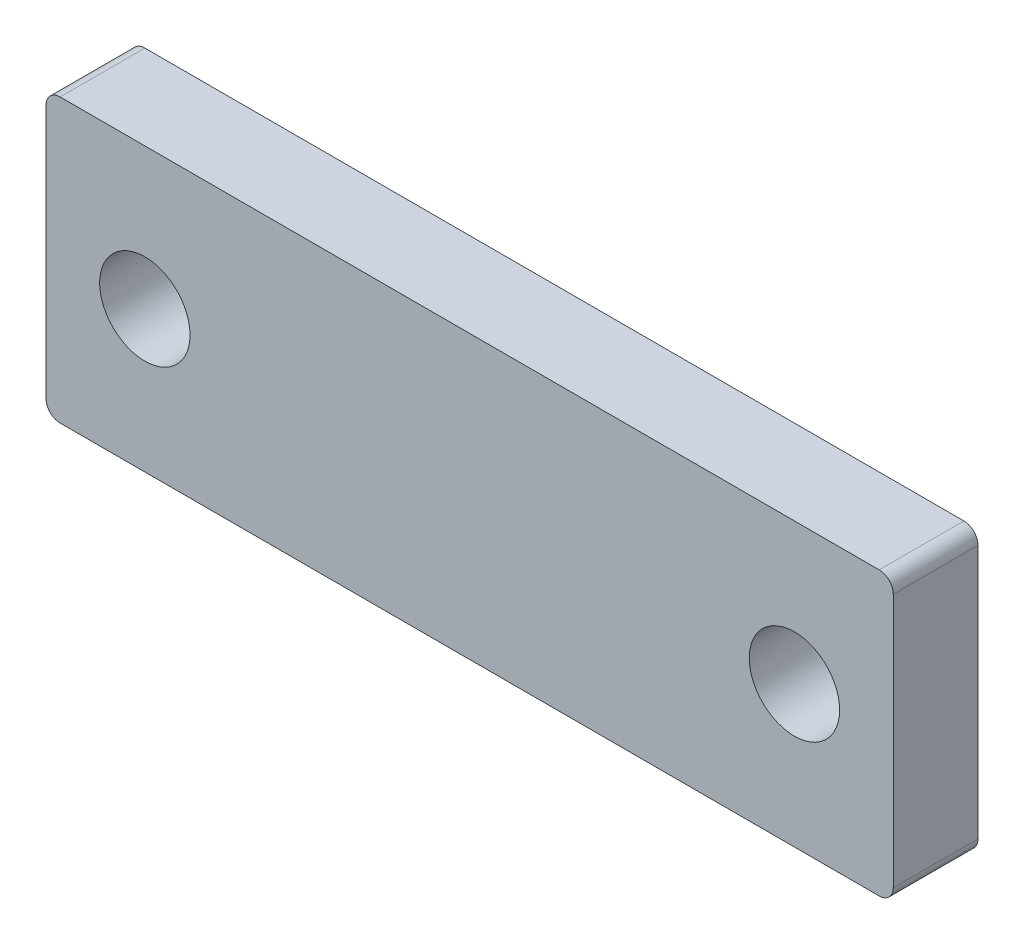
SolidWorks part; units mm, degrees
material "AISI 1045 Steel, cold drawn"
ref_plane "Front Plane" through (0, 0, 0) normal (0, 0, 1) x (1, 0, 0)
ref_plane "Top Plane" through (0, 0, 0) normal (0, 1, 0) x (1, 0, 0)
ref_plane "Right Plane" through (0, 0, 0) normal (1, 0, 0) x (0, 0, -1)
sketch "Sketch1" plane through (0, 0, 0) normal (0, 0, 1) x (1, 0, 0)
  line L0 (11.5, 0) -> (-11.5, 0) construction
  line L1 (15, -5) -> (-15, -5)
  line L2 (15, -5) -> (15, 5)
  line L3 (15, 5) -> (-15, 5)
  line L4 (-15, -5) -> (-15, 5)
  line L5 (15, -5) -> (-15, 5) construction
  line L6 (15, 5) -> (-15, -5) construction
  point P0 (0, 0)
  point P9 (0, 0)
  dimension "D1" = 10
  dimension "D2" = 30
  dimension "D3" = 23
extrude "Boss-Extrude1" add sketch "Sketch1" along normal blind 3
hole_wizard "M3 Clearance Hole1" positions "Sketch2" profile "Sketch3" hole size "M3" standard "ANSI Metric" end condition through all
sketch "Sketch2" plane through (0, 0, 3) normal (0, 0, 1) x (1, 0, 0)
  point P0 (-11.5, 0)
  point P3 (11.5, 0)
sketch "Sketch3" plane through (-11.5, 0, 3) normal (1, 0, 0) x (0, -1, 0)
  line L0 (0, 0) -> (0, 3)
  line L1 (0, 3) -> (1.6, 3)
  line L2 (1.6, 3) -> (1.6, 0)
  line L5 (1.6, 0) -> (0, 0)
  line L11 (0, -6.35) -> (0, 107.95) construction
  dimension "Thru Hole Dia." = 3.2
  dimension "Thru Hole Depth" = 3
fillet "Fillet1" radius 0.5 4 edges at (15, 5, 1.5) (15, -5, 1.5) (-15, -5, 1.5) (-15, 5, 1.5)
